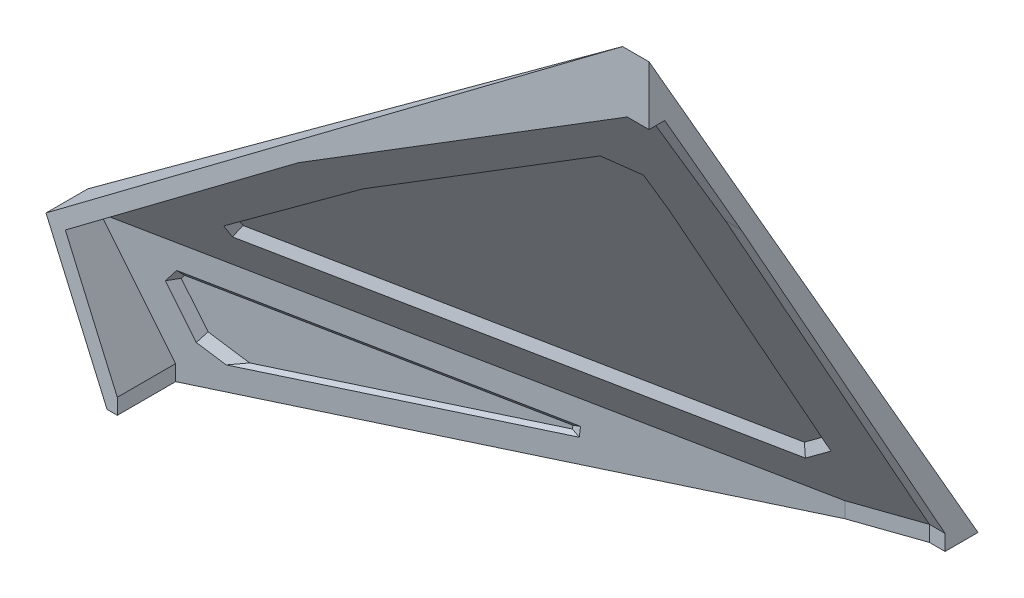
SolidWorks part; units mm, degrees
ref_plane "Plan de face" through (0, 0, 0) normal (0, 0, 1) x (1, 0, 0)
ref_plane "Plan de dessus" through (0, 0, 0) normal (0, 1, 0) x (1, 0, 0)
ref_plane "Plan de droite" through (0, 0, 0) normal (1, 0, 0) x (0, 0, -1)
sketch "Esquisse1" plane through (0, 0, 0) normal (0, 0, 1) x (1, 0, 0)
  line L0 (0, 0) -> (0, 300)
  line L1 (0, 300) -> (-400, 0) construction
  line L2 (-400, 0) -> (0, 0)
  line L3 (0, 300) -> (0, 377.9)
  line L4 (0, 377.9) -> (-400, 77.9)
  line L5 (-400, 77.9) -> (-400, 0)
  dimension "D1" = 300
  dimension "D2" = 400
  dimension "D3" = 77.9
extrude "Boss.-Extru.1" add sketch "Esquisse1" along normal blind 220
sketch "Esquisse2" plane through (0, 0, 0) normal (1, 0, 0) x (0, 0, -1)
  line L0 (-240, 400) -> (-10, 0)
  line L1 (-220, 0) -> (0, 0) construction
  line L2 (-10, 0) -> (0, 0)
  line L3 (0, 0) -> (0, 377.9)
  line L4 (0, 377.9) -> (0, 400)
  line L5 (0, 400) -> (-240, 400)
  line L6 (-10, 0) -> (-10, 400) construction
  dimension "D1" = 400
  dimension "D2" = 230
  dimension "D3" = 10
extrude "Enlèv. mat.-Extru.1" cut sketch "Esquisse2" against normal through all
sketch "Esquisse9" plane through (0, 0, 0) normal (0, -1, 0) x (-1, 0, 0)
  line L0 (0, -10) -> (546, -270)
  line L1 (546, -270) -> (546, -10)
  line L2 (546, -10) -> (0, -10)
  dimension "D1" = 546
  dimension "D2" = 260
extrude "Enlèv. mat.-Extru.7" cut sketch "Esquisse9" against normal through all
sketch "Esquisse10" plane through (0, 0, 220) normal (0, 0, 1) x (1, 0, 0)
  line L0 (-400, 77.9) -> (-385, 89.15)
  line L1 (-16.9101, 365.2174) -> (-400, 77.9) construction
  line L2 (-385, 89.15) -> (15, -825.85)
  line L3 (15, -825.85) -> (-400, -825.85)
  line L4 (-400, -825.85) -> (-400, 77.9)
  line L5 (-385, 89.15) -> (-385, -825.85) construction
  dimension "D1" = 915
  dimension "D2" = 400
  dimension "D3" = 15
extrude "Enlèv. mat.-Extru.8" cut sketch "Esquisse10" against normal through all
ref_plane "Plan1" through (2.4204, -3.9014, 6.98) normal (-0.2897, 0.467, -0.8355) x (-0.9571, -0.1413, 0.2529)
sketch "Esquisse11" plane through (2.4204, -3.9014, 6.98) normal (-0.2897, 0.467, -0.8355) x (-0.9571, -0.1413, 0.2529)
  line L0 (411.5229, 185.1573) -> (386.8228, 107.3384)
  line L1 (386.8228, 107.3384) -> (375.386, 85.273)
  line L2 (375.386, 85.273) -> (2.5289, 4.879)
  line L3 (2.5289, 4.879) -> (4.0117, 426.1361)
  line L4 (4.0117, 426.1361) -> (20.1967, 426.1361)
  line L5 (20.1967, 426.1361) -> (411.5229, 185.1573)
extrude "Enlèv. mat.-Extru.9" cut sketch "Esquisse11" along normal through all
shell "Coque2" thickness 10
sketch "Esquisse12" plane through (0, 0, 0) normal (1, 0, 0) x (0, 0, -1)
  line L0 (-220, 0) -> (-31.0265, 0)
  line L1 (-220, 0) -> (-10, 0) construction
  line L2 (-31.0265, 0) -> (-31.0265, 10)
  line L3 (-31.0265, 10) -> (-161.2681, 243.0136)
  line L4 (-161.2681, 243.0136) -> (-210, 327.7647)
  line L5 (-220, 0) -> (-220, 365.2174) construction
  line L6 (-220, 327.7647) -> (-220, 0)
  line L7 (-210, 327.7647) -> (-220, 327.7647)
extrude "Enlèv. mat.-Extru.10" cut sketch "Esquisse12" against normal blind 10
sketch "Esquisse13" plane through (0, 0, 220) normal (0, 0, 1) x (1, 0, 0)
  line L0 (-10, 327.7647) -> (-13.9241, 327.7647)
  line L1 (-13.9241, 327.7647) -> (-223.7203, 197.6098)
  line L2 (-223.7203, 197.6098) -> (-372.6657, 85.9007)
  line L3 (-372.6657, 85.9007) -> (-339.4851, 10)
  line L4 (-339.4851, 10) -> (-339.4851, 0)
  line L5 (-346.0273, 0) -> (-10, 0) construction
  line L6 (-339.4851, 0) -> (0, 0)
  line L7 (0, 0) -> (0, 327.7647)
  line L9 (0, 327.7647) -> (-10, 327.7647)
  line L10 (0, 243.0136) -> (0, 327.7647) construction
extrude "Enlèv. mat.-Extru.11" cut sketch "Esquisse13" against normal blind 10
sketch "Esquisse14" plane through (0, 10, 0) normal (0, 1, 0) x (1, 0, 0)
  line L0 (-10, -31.0265) -> (-50.0889, -44.9278)
  line L1 (-339.4851, -182.7355) -> (-339.4851, -210)
  line L2 (-339.4851, -210) -> (-10, -210)
  line L3 (-10, -210) -> (-10, -31.0265)
  line L4 (-50.0889, -44.9278) -> (-339.4851, -182.7355)
extrude "Enlèv. mat.-Extru.12" cut sketch "Esquisse14" against normal blind 10
sketch "Esquisse15" plane through (5.3175, -8.5712, 15.3347) normal (0.2897, -0.467, 0.8355) x (0.9571, 0.1413, -0.2529)
  line L7 (-47.2662, 320.279) -> (-65.8608, 331.058)
  line L8 (-64.4708, 65.8766) -> (-46.0038, 78.1975)
  line L9 (-324.2649, 182.8874) -> (-323.3758, 173.5369)
  line L14 (-46.0038, 290.1804) -> (-48.1042, 340.2615)
  line L15 (-48.1042, 340.2615) -> (-224.0889, 249.0465)
  line L16 (-224.0889, 249.0465) -> (-332.6093, 177.3765)
  line L17 (-332.6093, 177.3765) -> (-49.6197, 59.7011)
  line L18 (-49.6197, 59.7011) -> (-46.0038, 59.1155)
  line L19 (-46.0038, 59.1155) -> (-46.0038, 290.1804)
  line L20 (-46.0038, 290.1804) -> (-47.2662, 320.279)
  line L21 (-65.8608, 331.058) -> (-224.0889, 249.0465)
  line L22 (-224.0889, 249.0465) -> (-324.2649, 182.8874)
  line L23 (-323.3758, 173.5369) -> (-64.4708, 65.8766)
  line L25 (-46.0038, 78.1975) -> (-46.0038, 290.1804)
  point P5 (-46.0038, 58.1975)
  dimension "D1" = 30
extrude "Enlèv. mat.-Extru.13" cut sketch "Esquisse15" against normal blind 5
sketch "Esquisse16" plane through (8.181, 0, 17.1802) normal (0.4299, 0, 0.9029) x (0.9029, 0, -0.4299)
  line L5 (-191.7545, 15) -> (-191.1197, 21.1392)
  line L6 (-384.5862, 61.5863) -> (-390.0166, 54.6322)
  line L7 (-375.1849, 24.0005) -> (-360.827, 15)
  line L10 (-394.3746, 63.6327) -> (-370.827, 15)
  line L11 (-370.827, 15) -> (-161.7545, 15)
  line L12 (-161.7545, 15) -> (-394.3746, 63.6327)
  line L13 (-390.0166, 54.6322) -> (-375.1849, 24.0005)
  line L14 (-360.827, 15) -> (-191.7545, 15)
  line L15 (-191.1197, 21.1392) -> (-384.5862, 61.5863)
  dimension "D1" = 15
extrude "Enlèv. mat.-Extru.14" cut sketch "Esquisse16" against normal blind 5
chamfer "Chanfrein1" distance 5 angle 45 13 edges at (-40.162, 148.0393, 112.6571) (-48.9995, 48.837, 60.273) (-181.738, 70.8447, 118.6028) (-306.0644, 103.5532, 179.9967) (-258.5499, 143.5264, 185.8633) (-134.8887, 226.4579, 189.3363) (-50.2688, 270.0441, 184.3556) (-40.7661, 253.6065, 171.8727) (-326.2267, 19.5002, 170.884) (-339.4038, 39.3164, 177.1588) (-343.6478, 58.1093, 179.1798) (-253.8597, 41.3628, 136.4235) (-166.8096, 18.0696, 94.9711)
